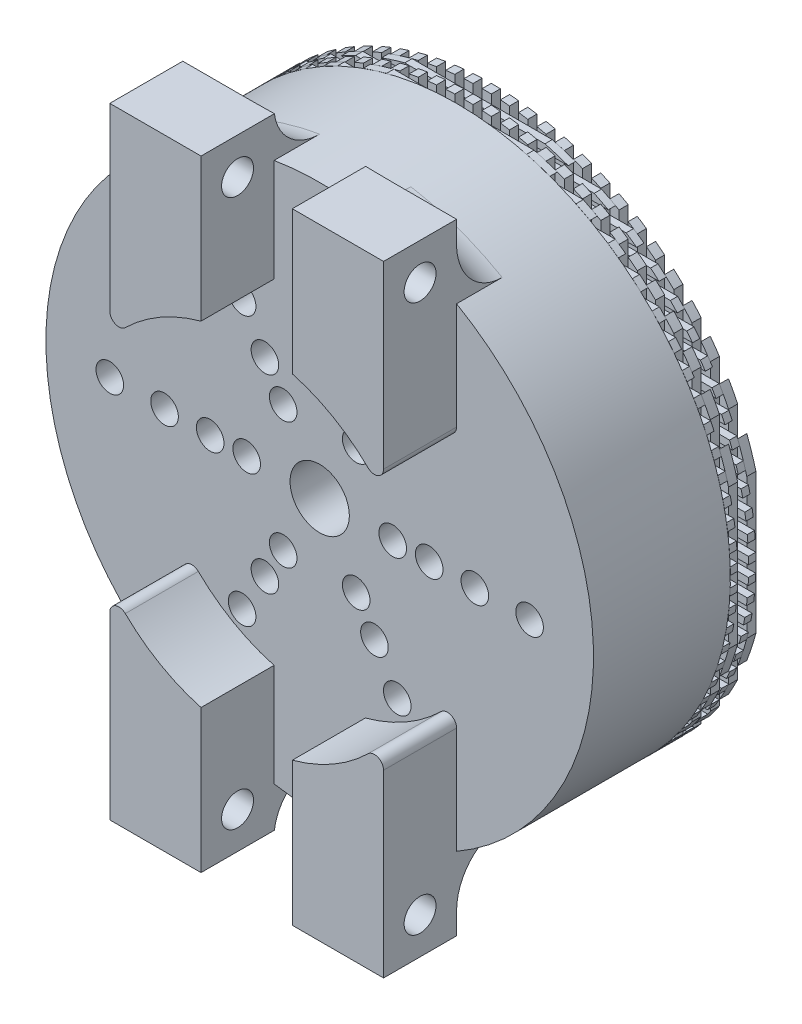
SolidWorks part; units mm, degrees
ref_plane "Front Plane" through (0, 0, 0) normal (1, 0, 0) x (0, 1, 0)
ref_plane "Top Plane" through (0, 0, 0) normal (0, 0, 1) x (0, 1, 0)
ref_plane "Right Plane" through (0, 0, 0) normal (0, 1, 0) x (-1, 0, 0)
sketch "Sketch1" plane through (0, 0, 0) normal (1, 0, 0) x (0, 1, 0)
  line L0 (64, -4) -> (68, -4) construction
  line L1 (0, 0) -> (68, 0)
  line L2 (0, 0) -> (0, -8)
  line L3 (0, -8) -> (68, -8)
  line L4 (68, 0) -> (68, -8)
  line L5 (4, -4) -> (0, -4) construction
  circle A0 centre (4, -4) radius 1.75
  circle A1 centre (64, -4) radius 1.75
  point P10 (0, -4)
  dimension "D1" = 3.5
  dimension "D2" = 60
  dimension "D3" = 8
  dimension "D4" = 4
extrude "Boss-Extrude1" add sketch "Sketch1" along normal blind 30
sketch "Sketch3" plane through (0, 0, -8) normal (0, 0, -1) x (1, 0, 0)
  line L1 (30, 0) -> (30, -68) construction
  line L2 (15, -34) -> (30, -34) construction
  line L3 (15, -34) -> (0, -34) construction
  line L4 (0, 0) -> (0, -68) construction
  circle A0 centre (15, -34) radius 30
  dimension "D1" = 60
extrude "Boss-Extrude2" add sketch "Sketch3" along normal blind 15
sketch "Sketch4" plane through (0, 0, 0) normal (0, 0, 1) x (1, 0, 0)
  circle A0 centre (15, 34) radius 19
  dimension "D1" = 38
extrude "Cut-Extrude1" cut sketch "Sketch4" against normal up to surface (8 mm away) and the other way through all up to face at (37.5, 34, -8)
ref_plane "Plane1" through (15, 0, 0) normal (1, 0, 0) x (0, 0, -1)
sketch "Sketch5" plane through (15, 0, 0) normal (1, 0, 0) x (0, 0, -1)
  line L0 (23, 4) -> (23, 64) construction
  line L1 (23, 63) -> (23.8, 63)
  line L2 (23, 63) -> (23, 62.2)
  line L3 (23, 62.2) -> (23.8, 62.2)
  line L4 (23.8, 63) -> (23.8, 62.2)
  line L5 (23, 64) -> (8, 64) construction
  line L6 (23, 61) -> (23, 60.2)
  line L7 (23, 61) -> (23.8, 61)
  line L8 (23.8, 61) -> (23.8, 60.2)
  line L9 (23, 60.2) -> (23.8, 60.2)
  line L10 (23, 59) -> (23, 58.2)
  line L11 (23, 59) -> (23.8, 59)
  line L12 (23.8, 59) -> (23.8, 58.2)
  line L13 (23, 58.2) -> (23.8, 58.2)
  line L14 (23, 57) -> (23, 56.2)
  line L15 (23, 57) -> (23.8, 57)
  line L16 (23.8, 57) -> (23.8, 56.2)
  line L17 (23, 56.2) -> (23.8, 56.2)
  line L18 (23, 55) -> (23, 54.2)
  line L19 (23, 55) -> (23.8, 55)
  line L20 (23.8, 55) -> (23.8, 54.2)
  line L21 (23, 54.2) -> (23.8, 54.2)
  line L22 (23, 53) -> (23, 52.2)
  line L23 (23, 53) -> (23.8, 53)
  line L24 (23.8, 53) -> (23.8, 52.2)
  line L25 (23, 52.2) -> (23.8, 52.2)
  line L26 (23, 51) -> (23, 50.2)
  line L27 (23, 51) -> (23.8, 51)
  line L28 (23.8, 51) -> (23.8, 50.2)
  line L29 (23, 50.2) -> (23.8, 50.2)
  line L30 (23, 49) -> (23, 48.2)
  line L31 (23, 49) -> (23.8, 49)
  line L32 (23.8, 49) -> (23.8, 48.2)
  line L33 (23, 48.2) -> (23.8, 48.2)
  line L34 (23, 47) -> (23, 46.2)
  line L35 (23, 47) -> (23.8, 47)
  line L36 (23.8, 47) -> (23.8, 46.2)
  line L37 (23, 46.2) -> (23.8, 46.2)
  line L38 (23, 45) -> (23, 44.2)
  line L39 (23, 45) -> (23.8, 45)
  line L40 (23.8, 45) -> (23.8, 44.2)
  line L41 (23, 44.2) -> (23.8, 44.2)
  line L42 (23, 43) -> (23, 42.2)
  line L43 (23, 43) -> (23.8, 43)
  line L44 (23.8, 43) -> (23.8, 42.2)
  line L45 (23, 42.2) -> (23.8, 42.2)
  line L46 (23, 41) -> (23, 40.2)
  line L47 (23, 41) -> (23.8, 41)
  line L48 (23.8, 41) -> (23.8, 40.2)
  line L49 (23, 40.2) -> (23.8, 40.2)
  line L50 (23, 39) -> (23, 38.2)
  line L51 (23, 39) -> (23.8, 39)
  line L52 (23.8, 39) -> (23.8, 38.2)
  line L53 (23, 38.2) -> (23.8, 38.2)
  line L54 (23, 37) -> (23, 36.2)
  line L55 (23, 37) -> (23.8, 37)
  line L56 (23.8, 37) -> (23.8, 36.2)
  line L57 (23, 36.2) -> (23.8, 36.2)
  line L58 (23, 35) -> (23, 34.2)
  line L59 (23, 35) -> (23.8, 35)
  line L60 (23.8, 35) -> (23.8, 34.2)
  line L61 (23, 34.2) -> (23.8, 34.2)
  line L62 (23, 33) -> (23, 32.2)
  line L63 (23, 33) -> (23.8, 33)
  line L64 (23.8, 33) -> (23.8, 32.2)
  line L65 (23, 32.2) -> (23.8, 32.2)
  line L66 (23, 31) -> (23, 30.2)
  line L67 (23, 31) -> (23.8, 31)
  line L68 (23.8, 31) -> (23.8, 30.2)
  line L69 (23, 30.2) -> (23.8, 30.2)
  line L70 (23, 29) -> (23, 28.2)
  line L71 (23, 29) -> (23.8, 29)
  line L72 (23.8, 29) -> (23.8, 28.2)
  line L73 (23, 28.2) -> (23.8, 28.2)
  line L74 (23, 27) -> (23, 26.2)
  line L75 (23, 27) -> (23.8, 27)
  line L76 (23.8, 27) -> (23.8, 26.2)
  line L77 (23, 26.2) -> (23.8, 26.2)
  line L78 (23, 25) -> (23, 24.2)
  line L79 (23, 25) -> (23.8, 25)
  line L80 (23.8, 25) -> (23.8, 24.2)
  line L81 (23, 24.2) -> (23.8, 24.2)
  line L82 (23, 23) -> (23, 22.2)
  line L83 (23, 23) -> (23.8, 23)
  line L84 (23.8, 23) -> (23.8, 22.2)
  line L85 (23, 22.2) -> (23.8, 22.2)
  line L86 (23, 21) -> (23, 20.2)
  line L87 (23, 21) -> (23.8, 21)
  line L88 (23.8, 21) -> (23.8, 20.2)
  line L89 (23, 20.2) -> (23.8, 20.2)
  line L90 (23, 19) -> (23, 18.2)
  line L91 (23, 19) -> (23.8, 19)
  line L92 (23.8, 19) -> (23.8, 18.2)
  line L93 (23, 18.2) -> (23.8, 18.2)
  line L94 (23, 17) -> (23, 16.2)
  line L95 (23, 17) -> (23.8, 17)
  line L96 (23.8, 17) -> (23.8, 16.2)
  line L97 (23, 16.2) -> (23.8, 16.2)
  line L98 (23, 15) -> (23, 14.2)
  line L99 (23, 15) -> (23.8, 15)
  line L100 (23.8, 15) -> (23.8, 14.2)
  line L101 (23, 14.2) -> (23.8, 14.2)
  line L102 (23, 13) -> (23, 12.2)
  line L103 (23, 13) -> (23.8, 13)
  line L104 (23.8, 13) -> (23.8, 12.2)
  line L105 (23, 12.2) -> (23.8, 12.2)
  line L106 (23, 11) -> (23, 10.2)
  line L107 (23, 11) -> (23.8, 11)
  line L108 (23.8, 11) -> (23.8, 10.2)
  line L109 (23, 10.2) -> (23.8, 10.2)
  line L110 (23, 9) -> (23, 8.2)
  line L111 (23, 9) -> (23.8, 9)
  line L112 (23.8, 9) -> (23.8, 8.2)
  line L113 (23, 8.2) -> (23.8, 8.2)
  line L114 (23, 7) -> (23, 6.2)
  line L115 (23, 7) -> (23.8, 7)
  line L116 (23.8, 7) -> (23.8, 6.2)
  line L117 (23, 6.2) -> (23.8, 6.2)
  line L118 (23, 5) -> (23, 4.2)
  line L119 (23, 5) -> (23.8, 5)
  line L120 (23.8, 5) -> (23.8, 4.2)
  line L121 (23, 4.2) -> (23.8, 4.2)
  line L122 (23, 3) -> (23, 2.2)
  line L123 (23, 3) -> (23.8, 3)
  line L124 (23.8, 3) -> (23.8, 2.2)
  line L125 (23, 2.2) -> (23.8, 2.2)
  line L126 (23, 63) -> (23, 61) construction
  dimension "D1" = 0.8
  dimension "D2" = 1
  dimension "D4" = 2
  dimension "D3" = 31
extrude "Boss-Extrude3" add sketch "Sketch5" along normal mid plane 75 separate body
ref_plane "Plane2" through (0, 34, 0) normal (0, -1, 0) x (-1, 0, 0)
sketch "Sketch6" plane through (0, 34, 0) normal (0, -1, 0) x (-1, 0, 0)
  line L0 (-52.5, 23.8) -> (22.5, 23.8) construction
  line L1 (-44, 23.8) -> (-43, 23.8)
  line L2 (-44, 23.8) -> (-44, 24.8)
  line L3 (-44, 24.8) -> (-43, 24.8)
  line L4 (-43, 23.8) -> (-43, 24.8)
  line L5 (-45, 23) -> (-45, 8) construction
  line L6 (-42, 23.8) -> (-42, 24.8)
  line L7 (-42, 23.8) -> (-41, 23.8)
  line L8 (-41, 23.8) -> (-41, 24.8)
  line L9 (-42, 24.8) -> (-41, 24.8)
  line L10 (-40, 23.8) -> (-40, 24.8)
  line L11 (-40, 23.8) -> (-39, 23.8)
  line L12 (-39, 23.8) -> (-39, 24.8)
  line L13 (-40, 24.8) -> (-39, 24.8)
  line L14 (-38, 23.8) -> (-38, 24.8)
  line L15 (-38, 23.8) -> (-37, 23.8)
  line L16 (-37, 23.8) -> (-37, 24.8)
  line L17 (-38, 24.8) -> (-37, 24.8)
  line L18 (-36, 23.8) -> (-36, 24.8)
  line L19 (-36, 23.8) -> (-35, 23.8)
  line L20 (-35, 23.8) -> (-35, 24.8)
  line L21 (-36, 24.8) -> (-35, 24.8)
  line L22 (-34, 23.8) -> (-34, 24.8)
  line L23 (-34, 23.8) -> (-33, 23.8)
  line L24 (-33, 23.8) -> (-33, 24.8)
  line L25 (-34, 24.8) -> (-33, 24.8)
  line L26 (-32, 23.8) -> (-32, 24.8)
  line L27 (-32, 23.8) -> (-31, 23.8)
  line L28 (-31, 23.8) -> (-31, 24.8)
  line L29 (-32, 24.8) -> (-31, 24.8)
  line L30 (-30, 23.8) -> (-30, 24.8)
  line L31 (-30, 23.8) -> (-29, 23.8)
  line L32 (-29, 23.8) -> (-29, 24.8)
  line L33 (-30, 24.8) -> (-29, 24.8)
  line L34 (-28, 23.8) -> (-28, 24.8)
  line L35 (-28, 23.8) -> (-27, 23.8)
  line L36 (-27, 23.8) -> (-27, 24.8)
  line L37 (-28, 24.8) -> (-27, 24.8)
  line L38 (-26, 23.8) -> (-26, 24.8)
  line L39 (-26, 23.8) -> (-25, 23.8)
  line L40 (-25, 23.8) -> (-25, 24.8)
  line L41 (-26, 24.8) -> (-25, 24.8)
  line L42 (-24, 23.8) -> (-24, 24.8)
  line L43 (-24, 23.8) -> (-23, 23.8)
  line L44 (-23, 23.8) -> (-23, 24.8)
  line L45 (-24, 24.8) -> (-23, 24.8)
  line L46 (-22, 23.8) -> (-22, 24.8)
  line L47 (-22, 23.8) -> (-21, 23.8)
  line L48 (-21, 23.8) -> (-21, 24.8)
  line L49 (-22, 24.8) -> (-21, 24.8)
  line L50 (-20, 23.8) -> (-20, 24.8)
  line L51 (-20, 23.8) -> (-19, 23.8)
  line L52 (-19, 23.8) -> (-19, 24.8)
  line L53 (-20, 24.8) -> (-19, 24.8)
  line L54 (-18, 23.8) -> (-18, 24.8)
  line L55 (-18, 23.8) -> (-17, 23.8)
  line L56 (-17, 23.8) -> (-17, 24.8)
  line L57 (-18, 24.8) -> (-17, 24.8)
  line L58 (-16, 23.8) -> (-16, 24.8)
  line L59 (-16, 23.8) -> (-15, 23.8)
  line L60 (-15, 23.8) -> (-15, 24.8)
  line L61 (-16, 24.8) -> (-15, 24.8)
  line L62 (-14, 23.8) -> (-14, 24.8)
  line L63 (-14, 23.8) -> (-13, 23.8)
  line L64 (-13, 23.8) -> (-13, 24.8)
  line L65 (-14, 24.8) -> (-13, 24.8)
  line L66 (-12, 23.8) -> (-12, 24.8)
  line L67 (-12, 23.8) -> (-11, 23.8)
  line L68 (-11, 23.8) -> (-11, 24.8)
  line L69 (-12, 24.8) -> (-11, 24.8)
  line L70 (-10, 23.8) -> (-10, 24.8)
  line L71 (-10, 23.8) -> (-9, 23.8)
  line L72 (-9, 23.8) -> (-9, 24.8)
  line L73 (-10, 24.8) -> (-9, 24.8)
  line L74 (-8, 23.8) -> (-8, 24.8)
  line L75 (-8, 23.8) -> (-7, 23.8)
  line L76 (-7, 23.8) -> (-7, 24.8)
  line L77 (-8, 24.8) -> (-7, 24.8)
  line L78 (-6, 23.8) -> (-6, 24.8)
  line L79 (-6, 23.8) -> (-5, 23.8)
  line L80 (-5, 23.8) -> (-5, 24.8)
  line L81 (-6, 24.8) -> (-5, 24.8)
  line L82 (-4, 23.8) -> (-4, 24.8)
  line L83 (-4, 23.8) -> (-3, 23.8)
  line L84 (-3, 23.8) -> (-3, 24.8)
  line L85 (-4, 24.8) -> (-3, 24.8)
  line L86 (-2, 23.8) -> (-2, 24.8)
  line L87 (-2, 23.8) -> (-1, 23.8)
  line L88 (-1, 23.8) -> (-1, 24.8)
  line L89 (-2, 24.8) -> (-1, 24.8)
  line L90 (0, 23.8) -> (0, 24.8)
  line L91 (0, 23.8) -> (1, 23.8)
  line L92 (1, 23.8) -> (1, 24.8)
  line L93 (0, 24.8) -> (1, 24.8)
  line L94 (2, 23.8) -> (2, 24.8)
  line L95 (2, 23.8) -> (3, 23.8)
  line L96 (3, 23.8) -> (3, 24.8)
  line L97 (2, 24.8) -> (3, 24.8)
  line L98 (4, 23.8) -> (4, 24.8)
  line L99 (4, 23.8) -> (5, 23.8)
  line L100 (5, 23.8) -> (5, 24.8)
  line L101 (4, 24.8) -> (5, 24.8)
  line L102 (6, 23.8) -> (6, 24.8)
  line L103 (6, 23.8) -> (7, 23.8)
  line L104 (7, 23.8) -> (7, 24.8)
  line L105 (6, 24.8) -> (7, 24.8)
  line L106 (8, 23.8) -> (8, 24.8)
  line L107 (8, 23.8) -> (9, 23.8)
  line L108 (9, 23.8) -> (9, 24.8)
  line L109 (8, 24.8) -> (9, 24.8)
  line L110 (10, 23.8) -> (10, 24.8)
  line L111 (10, 23.8) -> (11, 23.8)
  line L112 (11, 23.8) -> (11, 24.8)
  line L113 (10, 24.8) -> (11, 24.8)
  line L114 (12, 23.8) -> (12, 24.8)
  line L115 (12, 23.8) -> (13, 23.8)
  line L116 (13, 23.8) -> (13, 24.8)
  line L117 (12, 24.8) -> (13, 24.8)
  line L118 (14, 23.8) -> (14, 24.8)
  line L119 (14, 23.8) -> (15, 23.8)
  line L120 (15, 23.8) -> (15, 24.8)
  line L121 (14, 24.8) -> (15, 24.8)
  line L122 (16, 23.8) -> (16, 24.8)
  line L123 (16, 23.8) -> (17, 23.8)
  line L124 (17, 23.8) -> (17, 24.8)
  line L125 (16, 24.8) -> (17, 24.8)
  line L126 (-44, 23.8) -> (-42, 23.8) construction
  dimension "D1" = 1
  dimension "D2" = 1
  dimension "D4" = 2
  dimension "D3" = 31
extrude "Boss-Extrude4" add sketch "Sketch6" along normal mid plane 74 separate body
pattern_linear "LPattern1" count 2 spacing 2 along (0, 0, -1) of "Boss-Extrude3", "Boss-Extrude4"
sketch "Sketch7" plane through (0, 0, -8) normal (0, 0, -1) x (1, 0, 0)
  circle A0 centre (15, -34) radius 30
  circle A4 centre (15, -34) radius 30 construction
  circle A5 centre (15, -34) radius 72.5485
  dimension "D1" = 60
extrude "Cut-Extrude2" cut sketch "Sketch7" along normal through all contours A5 A0 region at (-55.4965, 34, -8)
fillet "Fillet3" radius 1 4 edges at (30, 22.3381, -4) (30, 45.6619, -4) (0, 45.6619, -4) (0, 22.3381, -4)
sketch "Sketch8" plane through (0, 0, 0) normal (0, 0, 1) x (1, 0, 0)
  line L0 (20, 34) -> (15, 34) construction
  line L1 (10, 71.5) -> (20, 71.5)
  line L2 (10, 71.5) -> (10, -3.5)
  line L3 (10, -3.5) -> (20, -3.5)
  line L4 (20, 71.5) -> (20, -3.5)
  line L5 (15, -13.3161) -> (15, 13.3161) construction
  line L6 (15, 34) -> (10, 34) construction
  line L7 (-10.9219, 34) -> (10.9219, 34) construction
  dimension "D1" = 10
  dimension "D2" = 75
extrude "Cut-Extrude3" cut sketch "Sketch8" against normal up to surface (8 mm away) up to face at (15, 34, -8)
fillet "Fillet1" radius 5 4 edges at (25.1607, 5.7731, -8) (4.8393, 5.7731, -8) (4.8393, 62.2269, -8) (25.1607, 62.2269, -8)
sketch "Sketch9" plane through (0, 0, -8) normal (0, 0, 1) x (1, 0, 0)
  circle A0 centre (15, 34) radius 3.25
  dimension "D1" = 6.5
extrude "Cut-Extrude4" cut sketch "Sketch9" against normal up to surface (15 mm away) up to face at (15, 64, -23)
sketch "Sketch10" plane through (0, 0, -23) normal (0, 0, -1) x (-1, 0, 0)
  line L0 (-15, 34) -> (-45, 34) construction
  circle A0 centre (-23, 34) radius 1.25
  circle A1 centre (-19, 40.9282) radius 1.25
  circle A2 centre (-15, 34) radius 8 construction
  circle A3 centre (-15, 34) radius 3.25 construction
  circle A4 centre (-15, 34) radius 30 construction
  circle A5 centre (-27, 34) radius 1.25
  circle A6 centre (-32, 34) radius 1.25
  circle A7 centre (-38, 34) radius 1.25
  circle A8 centre (-21, 44.3923) radius 1.25
  circle A9 centre (-23.5, 48.7224) radius 1.25
  circle A10 centre (-26.5, 53.9186) radius 1.25
  circle A11 centre (-11, 40.9282) radius 1.25
  circle A12 centre (-9, 44.3923) radius 1.25
  circle A13 centre (-6.5, 48.7224) radius 1.25
  circle A14 centre (-3.5, 53.9186) radius 1.25
  circle A15 centre (-7, 34) radius 1.25
  circle A16 centre (-3, 34) radius 1.25
  circle A17 centre (2, 34) radius 1.25
  circle A18 centre (8, 34) radius 1.25
  circle A19 centre (-11, 27.0718) radius 1.25
  circle A20 centre (-9, 23.6077) radius 1.25
  circle A21 centre (-6.5, 19.2776) radius 1.25
  circle A22 centre (-3.5, 14.0814) radius 1.25
  circle A23 centre (-19, 27.0718) radius 1.25
  circle A24 centre (-21, 23.6077) radius 1.25
  circle A25 centre (-23.5, 19.2776) radius 1.25
  circle A26 centre (-26.5, 14.0814) radius 1.25
  dimension "D1" = 2.5
  dimension "D2" = 16
  dimension "D3" = 4
  dimension "D4" = 5
  dimension "D5" = 6
  dimension "D6" = 6
extrude "Cut-Extrude5" cut sketch "Sketch10" against normal up to surface (15 mm away) draft 1 up to face at (18.25, 34, -8) draft outward yes
